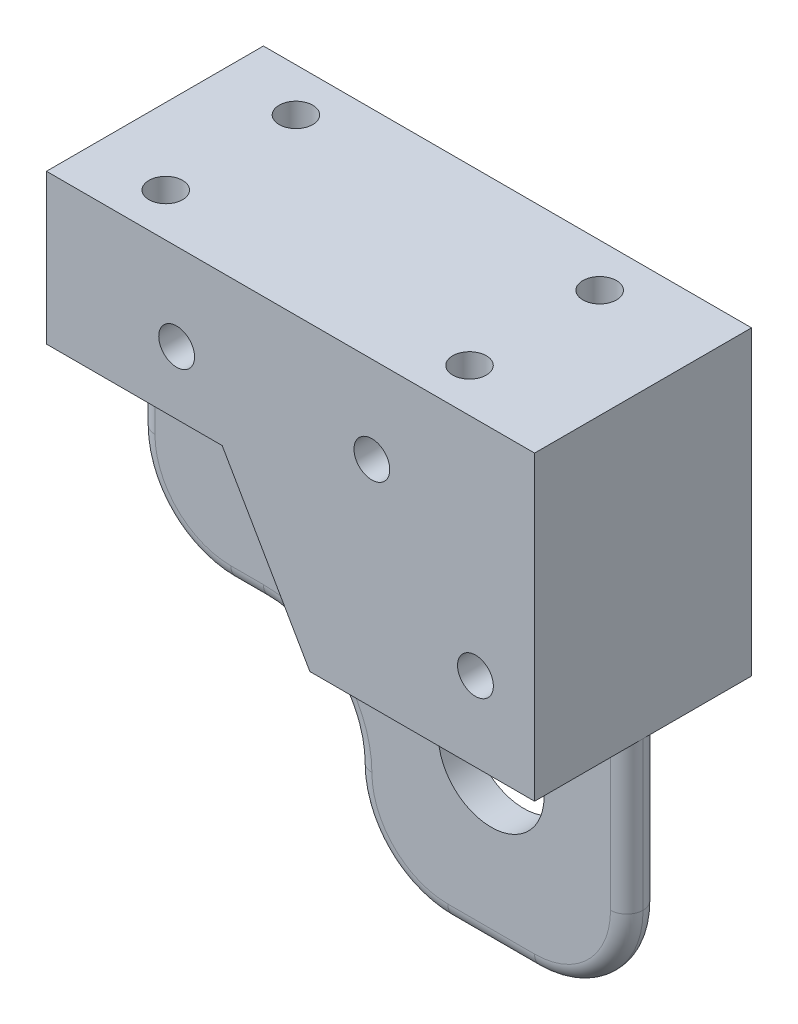
SolidWorks part; units mm, degrees
ref_plane "Front Plane" through (0, 0, 0) normal (0, 0, 1) x (1, 0, 0)
ref_plane "Top Plane" through (0, 0, 0) normal (0, 1, 0) x (1, 0, 0)
ref_plane "Right Plane" through (0, 0, 0) normal (1, 0, 0) x (0, 0, -1)
sketch "Sketch1" plane through (0, 0, 0) normal (0, 0, 1) x (1, 0, 0)
  line L0 (45, 12) -> (12.5, 12) construction
  line L3 (0, 32.5) -> (45, 32.5)
  line L5 (45, -17.5) -> (0, -17.5)
  line L6 (45, 32.5) -> (45, -17.5)
  line L14 (12.5, 12) -> (12.5, -3) construction
  line L15 (12.5, -3) -> (32.5, -3) construction
  line L16 (0, 32.5) -> (0, -17.5)
  circle A0 centre (12.5, 12) radius 4.875
  circle A1 centre (32.5, -3) radius 4.875
  dimension "D4" = 9.75
  dimension "D7" = 15
  dimension "D5" = 20.5
  dimension "D1" = 17.5
  dimension "D2" = 12.5
  dimension "D3" = 50
  dimension "D6" = 12.5
  dimension "D8" = 12.5
  dimension "D9" = 20
extrude "Boss-Extrude1" add sketch "Sketch1" along normal blind 3
sketch "Sketch3" plane through (0, 0, 0) normal (0, 0, -1) x (-1, 0, 0)
  line L0 (0, 32.5) -> (0, -17.5) construction
  line L1 (-45, 32.5) -> (0, 32.5)
  line L2 (-45, 32.5) -> (-45, 18.7)
  line L3 (-45, 18.7) -> (0, 18.7)
  line L4 (0, 32.5) -> (0, 18.7)
  dimension "D1" = 13.8
extrude "Boss-Extrude3" add sketch "Sketch3" along normal blind 8.5 and the other way blind 11.5
sketch "Sketch4" plane through (0, 0, 3) normal (0, 0, 1) x (1, 0, 0)
  line L0 (12.5, 12) -> (0, 12) construction
  line L1 (0, -17.5) -> (20, -17.5)
  line L2 (0, -17.5) -> (0, -0.5)
  line L3 (0, -0.5) -> (20, -0.5)
  line L4 (20, -17.5) -> (20, -0.5)
  line L5 (0, 18.7) -> (0, -17.5) construction
  line L6 (32.5, -3) -> (32.5, -17.5) construction
  line L7 (0, -17.5) -> (45, -17.5) construction
  dimension "D1" = 12.5
  dimension "D2" = 12.5
extrude "Cut-Extrude1" cut sketch "Sketch4" against normal up to next
sketch "Sketch5" plane through (0, 0, 0) normal (0, 0, -1) x (-1, 0, 0)
  line L0 (-32.5, -3) -> (-45, -3) construction
  line L5 (-45, -17.5) -> (-45, 18.7) construction
  line L6 (-24.2829, 4.7) -> (-16.2, 18.7)
  line L7 (-45, 18.7) -> (0, 18.7) construction
  line L8 (-16.2, 18.7) -> (-45, 18.7)
  line L9 (-45, 18.7) -> (-45, 4.7)
  line L11 (-24.2829, 4.7) -> (-45, 4.7)
  circle A0 centre (-12.5, 12) radius 6.5 construction
  dimension "D4" = 13
  dimension "D1" = 28.8
  dimension "D2" = 14
  dimension "D3" = 60
extrude "Boss-Extrude4" add sketch "Sketch5" along normal blind 8.5 and the other way blind 11.5
fillet "Fillet1" radius 2 2 edges at (16.2, 18.7, -4.25) (24.2829, 4.7, -4.25)
fillet "Fillet3" radius 8.5 4 edges at (20, -0.5, 1.5) (45, -17.5, 1.5) (0, -0.5, 1.5) (20, -17.5, 1.5)
sketch "Sketch13" plane through (0, 0, -8.5) normal (0, 0, -1) x (-1, 0, 0)
  line L0 (0, 24.5) -> (-45, 24.5) construction
  line L1 (0, 18.7) -> (0, 32.5) construction
  line L2 (-45, 32.5) -> (-45, 4.7) construction
  line L3 (0, 32.5) -> (-45, 32.5) construction
  circle A0 centre (-12, 24.5) radius 1.65
  circle A1 centre (-30, 24.5) radius 1.65
  circle A2 centre (-39.55, 12) radius 1.65
  dimension "D2" = 3.3
  dimension "D5" = 20.5
  dimension "D1" = 8
  dimension "D3" = 12
  dimension "D4" = 15
  dimension "D6" = 5.45
extrude "Cut-Extrude5" cut sketch "Sketch13" against normal through all
sketch "Sketch14" plane through (0, 32.5, 0) normal (0, 1, 0) x (1, 0, 0)
  line L0 (0, -7.5) -> (0, 4.5) construction
  line L1 (0, -11.5) -> (0, 8.5) construction
  line L2 (0, -1.5) -> (45, -1.5) construction
  line L3 (45, -11.5) -> (45, 8.5) construction
  line L4 (0, 4.5) -> (7, 4.5) construction
  line L5 (0, -7.5) -> (7, -7.5) construction
  line L6 (7, -7.5) -> (35, -7.5) construction
  line L7 (7, 4.5) -> (35, 4.5) construction
  circle A0 centre (7, 4.5) radius 1.55
  circle A1 centre (7, -7.5) radius 1.55
  circle A2 centre (35, -7.5) radius 1.55
  circle A3 centre (35, 4.5) radius 1.55
  dimension "D3" = 3.1
  dimension "D1" = 6
  dimension "D2" = 7
  dimension "D4" = 10
  dimension "D5" = 10
extrude "Cut-Extrude6" cut sketch "Sketch14" against normal through all
fillet "Fillet4" radius 1.5 16 edges at (45, -2.15, 0) (42.5104, -15.0104, 0) (32.5, -17.5, 0) (22.4896, -15.0104, 0) (17.5104, -2.9896, 0) (10, -0.5, 0) (2.4896, 1.9896, 0) (45, -2.15, 3) (42.5104, -15.0104, 3) (32.5, -17.5, 3) (22.4896, -15.0104, 3) (17.5104, -2.9896, 3) (10, -0.5, 3) (2.4896, 1.9896, 3) (0, 13.35, 0) (0, 13.35, 3)
sketch "Sketch15" plane through (0, 18.7, 0) normal (0, -1, 0) x (1, 0, 0)
  circle A0 centre (7, -4.5) radius 2.6
  circle A1 centre (7, 7.5) radius 2.6
  dimension "D1" = 5.2
extrude "Cut-Extrude7" cut sketch "Sketch15" against normal blind 7.4
sketch "Sketch16" plane through (0, 4.7, 0) normal (0, -1, 0) x (1, 0, 0)
  circle A0 centre (35, -4.5) radius 2.6
  circle A1 centre (35, 7.5) radius 2.6
  circle A2 centre (7, 7.5) radius 2.6 construction
extrude "Cut-Extrude8" cut sketch "Sketch16" against normal blind 21.4
